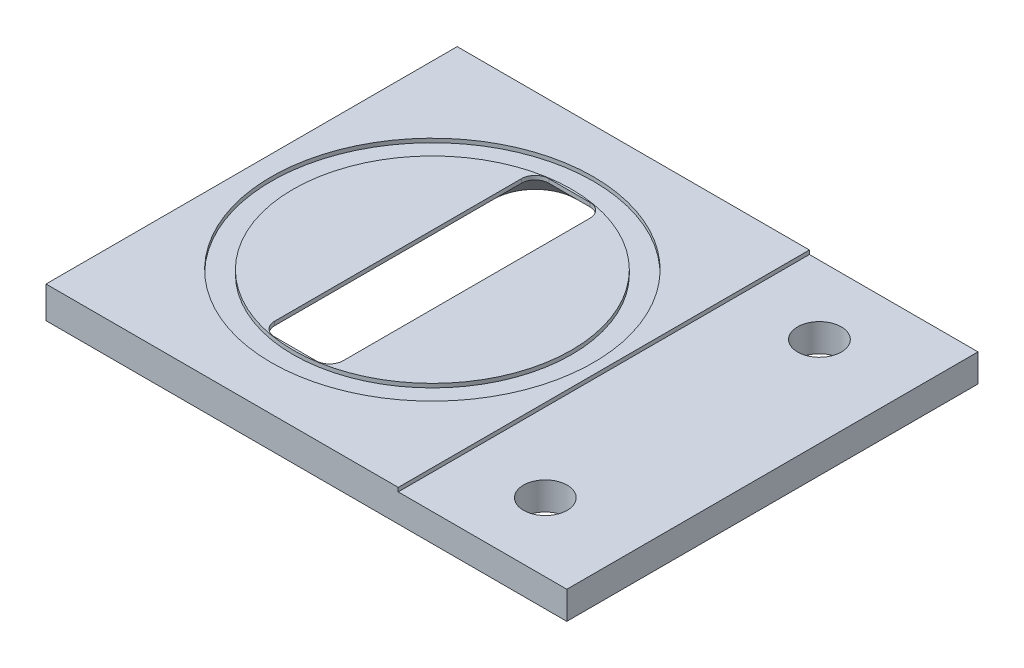
SolidWorks part; units mm, degrees
material "6061-T4 (SS)"
ref_plane "Front Plane" through (0, 0, 0) normal (0, 0, 1) x (1, 0, 0)
ref_plane "Top Plane" through (0, 0, 0) normal (0, 1, 0) x (1, 0, 0)
ref_plane "Right Plane" through (0, 0, 0) normal (1, 0, 0) x (0, 0, -1)
sketch "Sketch2" plane through (0, 0, 0) normal (0, 1, 0) x (1, 0, 0)
  line L5 (-13.189, 15) -> (24.811, 15)
  line L6 (-13.189, 15) -> (-13.189, -15)
  line L7 (-13.189, -15) -> (24.811, -15)
  line L8 (24.811, 15) -> (24.811, -15)
  line L9 (-13.189, 15) -> (24.811, -15) construction
  line L10 (-13.189, -15) -> (24.811, 15) construction
  dimension "D1" = 38
  dimension "D2" = 30
extrude "Boss-Extrude1" add sketch "Sketch2" along normal blind 2.032
sketch "Sketch4" plane through (0, 2.032, 0) normal (0, 1, 0) x (1, 0, 0)
  line L1 (1.5, -10) -> (-1.5, -10)
  line L2 (2.5, -9) -> (2.5, 9)
  line L3 (1.5, 10) -> (-1.5, 10)
  line L4 (-2.5, -9) -> (-2.5, 9)
  line L5 (2.5, -10) -> (-2.5, 10) construction
  line L6 (2.5, 10) -> (-2.5, -10) construction
  arc A0 (1.5, -10) -> (2.5, -9) centre (1.5, -9) ccw
  arc A1 (2.5, 9) -> (1.5, 10) centre (1.5, 9) ccw
  arc A2 (-1.5, 10) -> (-2.5, 9) centre (-1.5, 9) ccw
  arc A3 (-1.5, -10) -> (-2.5, -9) centre (-1.5, -9) cw
  point P0 (0, 0)
  dimension "D3" = 1
  dimension "D1" = 20
  dimension "D2" = 5
extrude "Cut-Extrude4" cut sketch "Sketch4" against normal through all draft 45 draft outward yes
sketch "Sketch5" plane through (0, 2.032, 0) normal (0, 1, 0) x (1, 0, 0)
  line L0 (18.2427, -15) -> (18.2427, 15) construction
  line L1 (-13.189, -15) -> (24.811, -15) construction
  line L2 (24.811, 15) -> (-13.189, 15) construction
  circle A0 centre (18.2427, -10) radius 1.595
  circle A1 centre (18.2427, 10) radius 1.595
  dimension "D3" = 3.19
  dimension "D4" = 3.19
  dimension "D1" = 5
  dimension "D2" = 5
extrude "Cut-Extrude5" cut sketch "Sketch5" against normal through all
sketch "Sketch6" plane through (0, 2.032, 0) normal (0, 1, 0) x (1, 0, 0)
  line L0 (0, 10.1625) -> (0, 11.75) construction
  line L1 (-13.189, -15) -> (12.511, -15)
  line L2 (-13.189, -15) -> (-13.189, 15)
  line L3 (-13.189, 15) -> (12.511, 15)
  line L4 (12.511, -15) -> (12.511, 15)
  line L5 (24.811, -15) -> (24.811, 15) construction
  line L6 (24.811, 15) -> (-13.189, 15) construction
  line L7 (0, -10) -> (1.5, -10)
  line L8 (-1.5, -10) -> (1.5, -10) construction
  line L9 (2.5, -9) -> (2.5, 9)
  line L10 (1.5, 10) -> (-1.5, 10)
  line L11 (-2.5, 9) -> (-2.5, -9)
  line L12 (-1.5, -10) -> (0, -10)
  line L13 (-2.5, 9) -> (-2.5, -9) construction
  line L14 (2.5, -9) -> (2.5, 9) construction
  line L15 (1.5, 10) -> (-1.5, 10) construction
  circle A0 centre (0, 0) radius 11.75
  circle A1 centre (0, 0) radius 10.1625
  circle A2 centre (0, 0) radius 11.75 construction
  arc A7 (-1.5, 10) -> (-2.5, 9) centre (-1.5, 9) ccw
  arc A8 (-1.5, 10) -> (-2.5, 9) centre (-1.5, 9) ccw construction
  arc A9 (2.5, 9) -> (1.5, 10) centre (1.5, 9) ccw
  arc A11 (2.5, 9) -> (1.5, 10) centre (1.5, 9) ccw construction
  arc A13 (-1.5, -10) -> (-2.5, -9) centre (-1.5, -9) cw
  arc A14 (-2.5, -9) -> (-1.5, -10) centre (-1.5, -9) ccw construction
  arc A15 (1.5, -10) -> (2.5, -9) centre (1.5, -9) ccw
  arc M1 (2.5, -9) -> (1.5, -10) centre (1.5, -9) cw
  line M2 (1.5, -10) -> (-1.5, -10)
  arc M3 (-1.5, -10) -> (-2.5, -9) centre (-1.5, -9) cw
  line M4 (-2.5, -9) -> (-2.5, 9)
  arc M5 (-2.5, 9) -> (-1.5, 10) centre (-1.5, 9) cw
  line M6 (-1.5, 10) -> (1.5, 10)
  arc M7 (1.5, 10) -> (2.5, 9) centre (1.5, 9) cw
  line M8 (2.5, 9) -> (2.5, -9)
  line M10 (24.811, 15) -> (-13.189, 15)
  line M11 (-13.189, 15) -> (-13.189, -15)
  line M12 (-13.189, -15) -> (24.811, -15)
  dimension "D1" = 1.5875
  dimension "D2" = 12.3
sketch "Sketch8" plane through (0, 2.032, 0) normal (0, 1, 0) x (1, 0, 0)
  line L0 (24.811, 15) -> (-13.189, 15) construction
  line L1 (-13.189, -15) -> (12.511, -15)
  line L2 (-13.189, -15) -> (-13.189, 15)
  line L3 (-13.189, 15) -> (12.511, 15)
  line L4 (12.511, -15) -> (12.511, 15)
  line L5 (24.811, -15) -> (24.811, 15) construction
  circle A0 centre (0, 0) radius 12.5
  circle A1 centre (0, 0) radius 12.5 construction
  dimension "D1" = 12.3
extrude "Boss-Extrude3" [suppressed] add sketch "Sketch8" along normal blind 2
extrude "Boss-Extrude4" add sketch "Sketch6" along normal blind 0.2874 contours L4 A0 M12 M10 M11 | A1 M8 M1 M2 M3 M4 M5 M6 M7 region at (-12.7939, 2.032, 0) region at (-9.8751, 2.032, 0)
